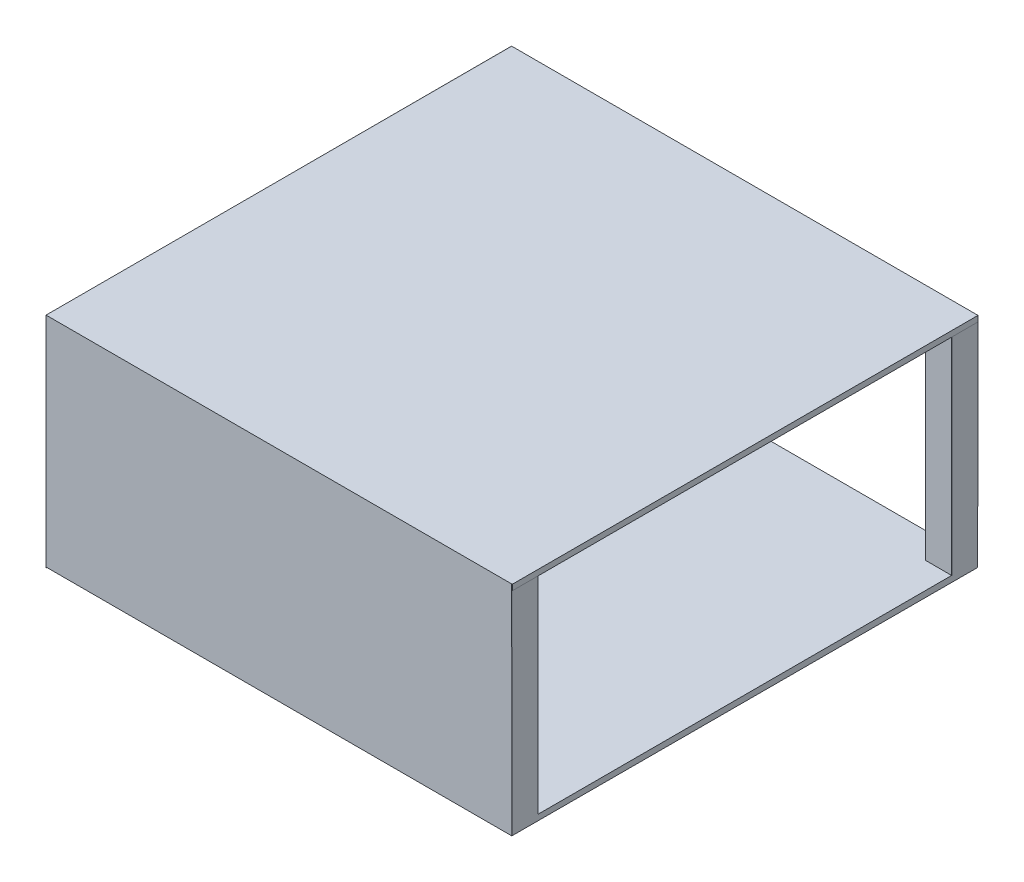
SolidWorks part; units mm, degrees
material "Pine"
ref_plane "Front Plane" through (0, 0, 0) normal (0, 0, 1) x (1, 0, 0)
ref_plane "Top Plane" through (0, 0, 0) normal (0, 1, 0) x (1, 0, 0)
ref_plane "Right Plane" through (0, 0, 0) normal (1, 0, 0) x (0, 0, -1)
sketch "Sketch1" plane through (0, 0, 0) normal (0, 1, 0) x (1, 0, 0)
  line L0 (-457.2, 457.2) -> (-457.2, 406.4)
  line L1 (-457.2, -457.2) -> (457.2, -457.2)
  line L2 (-457.2, -457.2) -> (-457.2, 457.2)
  line L3 (-457.2, 457.2) -> (457.2, 457.2)
  line L4 (457.2, -457.2) -> (457.2, 457.2)
  line L5 (-457.2, -457.2) -> (457.2, 457.2) construction
  line L6 (-457.2, 457.2) -> (457.2, -457.2) construction
  line L7 (-457.2, 457.2) -> (-406.4, 457.2)
  line L8 (-457.2, 406.4) -> (-406.4, 406.4)
  line L9 (-406.4, 457.2) -> (-406.4, 406.4)
  line L10 (457.2, 457.2) -> (457.2, 406.4)
  line L11 (457.2, 457.2) -> (406.4, 457.2)
  line L12 (457.2, 406.4) -> (406.4, 406.4)
  line L13 (406.4, 457.2) -> (406.4, 406.4)
  line L14 (457.2, -457.2) -> (457.2, -406.4)
  line L15 (457.2, -457.2) -> (406.4, -457.2)
  line L16 (457.2, -406.4) -> (406.4, -406.4)
  line L17 (406.4, -457.2) -> (406.4, -406.4)
  line L18 (-457.2, -457.2) -> (-406.4, -457.2)
  line L19 (-457.2, -457.2) -> (-457.2, -406.4)
  line L20 (-406.4, -457.2) -> (-406.4, -406.4)
  line L21 (-457.2, -406.4) -> (-406.4, -406.4)
  point P0 (0, 0)
  dimension "D1" = 914.4
  dimension "D2" = 914.4
  dimension "D3" = 50.8
  dimension "D4" = 50.8
  dimension "D5" = 50.8
  dimension "D6" = 50.8
  dimension "D7" = 50.8
  dimension "D8" = 50.8
  dimension "D9" = 50.8
  dimension "D10" = 50.8
extrude "Boss-Extrude1" add sketch "Sketch1" along normal blind 11.1125 contours L2 L21 L20 L1 L17 L16 L4 L12 L13 L3 L9 L8 region at (0, 0, 0)
extrude "Boss-Extrude3" add sketch "Sketch1<5>" along normal blind 417.5125 contours L14 L16 L17 L15
sketch "Sketch1<5>" plane through (0, 0, 0) normal (0, 1, 0) x (1, 0, 0) same geometry as "Sketch1"
extrude "Boss-Extrude4" add sketch "Sketch1<6>" along normal blind 417.5125 contours L19 L21 L20 L18
sketch "Sketch1<6>" plane through (0, 0, 0) normal (0, 1, 0) x (1, 0, 0) same geometry as "Sketch1"
extrude "Boss-Extrude5" add sketch "Sketch1<7>" along normal blind 417.5125 contours L11 L13 L12 L10
sketch "Sketch1<7>" plane through (0, 0, 0) normal (0, 1, 0) x (1, 0, 0) same geometry as "Sketch1"
extrude "Boss-Extrude6" add sketch "Sketch1<8>" along normal blind 417.5125 contours L0 L8 L9 L7
sketch "Sketch1<8>" plane through (0, 0, 0) normal (0, 1, 0) x (1, 0, 0) same geometry as "Sketch1"
sketch "Sketch2" plane through (0, 417.5125, 0) normal (0, 1, 0) x (1, 0, 0)
  line L0 (-457.2, 457.2) -> (-457.2, -457.2)
  line L1 (-457.2, 457.2) -> (458.6151, 457.2)
  line L2 (-457.2, -457.2) -> (458.6151, -457.2)
  line L3 (458.6151, 457.2) -> (458.6151, -457.2)
extrude "Boss-Extrude8" add sketch "Sketch2" along normal blind 11.1125
sketch "Sketch3" plane through (0, 0, 457.2) normal (0, 0, 1) x (1, 0, 0)
  line L0 (-457.2, 428.625) -> (-457.2, 0)
  line L1 (-457.2, 428.625) -> (457.2403, 428.625)
  line L2 (-457.2, 0) -> (457.2403, 0)
  line L3 (457.2403, 428.625) -> (457.2403, 0)
extrude "Boss-Extrude9" add sketch "Sketch3" along normal blind 0.4375
sketch "Sketch4" plane through (457.2, 0, 0) normal (1, 0, 0) x (0, 0, -1)
  line L0 (-457.2, 428.625) -> (-457.6375, 0)
  line L1 (-457.2, 428.625) -> (458.0179, 427.6908)
  line L2 (-457.6375, 0) -> (457.5804, -0.9342)
  line L3 (458.0179, 427.6908) -> (457.5804, -0.9342)
  line L4 (-406.4, 417.5125) -> (-406.4, 11.1125)
  line L5 (-406.4, 417.5125) -> (408.5101, 417.5125)
  line L6 (-406.4, 11.1125) -> (408.5101, 11.1125)
  line L7 (408.5101, 417.5125) -> (408.5101, 11.1125)
extrude "Boss-Extrude13" add sketch "Sketch4" along normal blind 0.4375
sketch "Sketch9" plane through (457.6375, 0, 0) normal (1, 0, 0) x (0, 0, -1)
  line L0 (-457.2, 428.625) -> (-457.6375, 0)
  line L1 (-457.2, 428.625) -> (459.0847, 427.6897)
  line L2 (-457.6375, 0) -> (458.6472, -0.9353)
  line L3 (459.0847, 427.6897) -> (458.6472, -0.9353)
sketch "Sketch10" plane through (-457.2, 0, 0) normal (-1, 0, 0) x (0, 0, 1)
  line L0 (-457.2, 428.625) -> (-457.5804, -0.9342)
  line L1 (-457.2, 428.625) -> (457.3338, 427.8152)
  line L2 (-457.5804, -0.9342) -> (456.9534, -1.744)
  line L3 (457.3338, 427.8152) -> (456.9534, -1.744)
extrude "Boss-Extrude21" add sketch "Sketch10" along normal blind 0.4375
